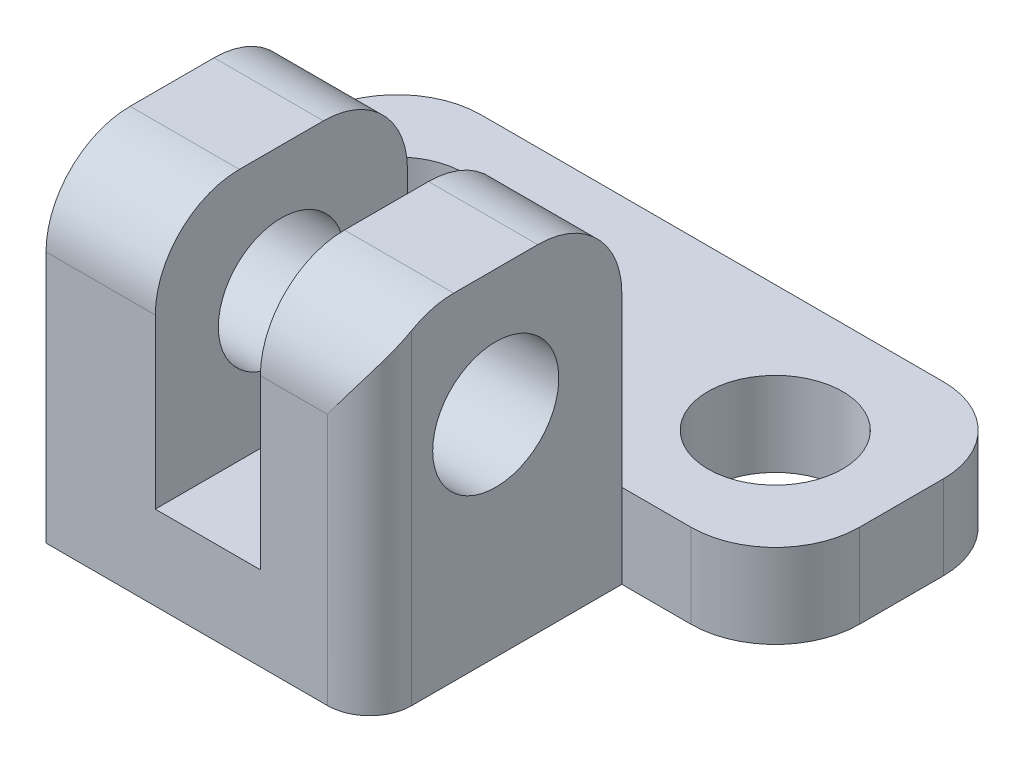
SolidWorks part; units mm, degrees
ref_plane "Front Plane" through (0, 0, 0) normal (0, 0, 1) x (1, 0, 0)
ref_plane "Top Plane" through (0, 0, 0) normal (0, 1, 0) x (1, 0, 0)
ref_plane "Right Plane" through (0, 0, 0) normal (1, 0, 0) x (0, 0, -1)
sketch "Sketch1" plane through (0, 0, 0) normal (0, 1, 0) x (1, 0, 0)
  line L1 (0, 0) -> (7.7, 0)
  line L2 (0, 0) -> (0, 6)
  line L3 (0, 6) -> (7.7, 6)
  line L4 (7.7, 0) -> (7.7, 6)
  dimension "D1" = 6
  dimension "D2" = 7.7
extrude "Boss-Extrude1" add sketch "Sketch1" along normal blind 8
sketch "Sketch2" plane through (0, 8, 0) normal (0, 1, 0) x (1, 0, 0)
  line L0 (3.85, 6) -> (3.85, 0) construction
  line L1 (7.7, 6) -> (0, 6) construction
  line L2 (0, 0) -> (7.7, 0) construction
  line L4 (2.6, 6) -> (5.1, 6)
  line L5 (2.6, 6) -> (2.6, 0)
  line L6 (2.6, 0) -> (5.1, 0)
  line L7 (5.1, 6) -> (5.1, 0)
  point P10 (3.85, 6)
  dimension "D1" = 2.5
extrude "Cut-Extrude1" cut sketch "Sketch2" against normal offset from surface (6 mm away) 2 up to face at (3.85, 0, -3)
sketch "Sketch3" plane through (5.1, 0, 0) normal (-1, 0, 0) x (0, 0, 1)
  line L0 (-6, 8) -> (0, 2) construction
  line L1 (0, 8) -> (-6, 2) construction
  point P8 (-3, 5)
  point P9 (0, 0)
  point P10 (0, 8)
  point P11 (0, 8)
  point P13 (-8, 8)
  point P15 (0, 2)
  point P17 (-8, 2)
hole_wizard "Ø3.0mm Dowel Hole1" positions "Sketch4" profile "Sketch5" hole size "Ø3.0" standard "ANSI Metric" end condition through all
sketch "Sketch4" plane through (0, 0, 0) normal (-1, 0, 0) x (0, 0, 1)
  point P0 (-3, 5)
sketch "Sketch5" plane through (0, 5, -3) normal (0, 1, 0) x (0, 0, 1)
  line L0 (0, 0) -> (0, 7.7)
  line L1 (0, 7.7) -> (1.5, 7.7)
  line L2 (1.5, 7.7) -> (1.5, 0)
  line L5 (1.5, 0) -> (0, 0)
  line L11 (0, -6.35) -> (0, 107.95) construction
  dimension "Thru Hole Dia." = 3
  dimension "Thru Hole Depth" = 7.7
sketch "Sketch7" plane through (0, 0, 0) normal (0, -1, 0) x (1, 0, 0)
  line L5 (7.7, -6) -> (0, -6) construction
  line L6 (-3.65, -6) -> (11.35, -6)
  line L7 (-3.65, -6) -> (-3.65, -12)
  line L8 (-3.65, -12) -> (11.35, -12)
  line L9 (11.35, -6) -> (11.35, -12)
  line L10 (3.85, 0) -> (3.85, -10.4099) construction
  line L11 (2.6, 0) -> (5.1, 0) construction
  point P10 (3.85, -12)
  dimension "D1" = 15
  dimension "D2" = 6
extrude "Boss-Extrude2" add sketch "Sketch7" against normal up to surface (2 mm away) up to face at (3.85, 2, -3)
sketch "Sketch8" plane through (0, 2, 0) normal (0, 1, 0) x (1, 0, 0)
  line L0 (-3.65, 9) -> (11.35, 9) construction
  line L1 (-3.65, 12) -> (-3.65, 6) construction
  line L2 (11.35, 6) -> (11.35, 12) construction
  point P6 (-0.65, 9)
  point P7 (8.35, 9)
  dimension "D1" = 3
  dimension "D2" = 3
hole_wizard "M3 Clearance Hole1" positions "Sketch9" profile "Sketch10" hole size "M3" standard "ANSI Metric" end condition through all
sketch "Sketch9" plane through (0, 2, 0) normal (0, 1, 0) x (1, 0, 0)
  point P0 (-0.65, 9)
  point P3 (8.35, 9)
sketch "Sketch10" plane through (-0.65, 2, -9) normal (1, 0, 0) x (0, 0, 1)
  line L0 (0, 0) -> (0, 2)
  line L1 (0, 2) -> (1.6, 2)
  line L2 (1.6, 2) -> (1.6, 0)
  line L5 (1.6, 0) -> (0, 0)
  line L11 (0, -6.35) -> (0, 107.95) construction
  dimension "Thru Hole Dia." = 3.2
  dimension "Thru Hole Depth" = 2
fillet "Fillet1" radius 2 8 edges at (6.4, 8, -6) (1.3, 8, -6) (6.4, 8, 0) (1.3, 8, 0) (-3.65, 1, -6) (11.35, 1, -6) (11.35, 1, -12) (-3.65, 1, -12)
fillet "Fillet2" radius 1 1 edges at (7.7, 3, 0) tangent propagation no
